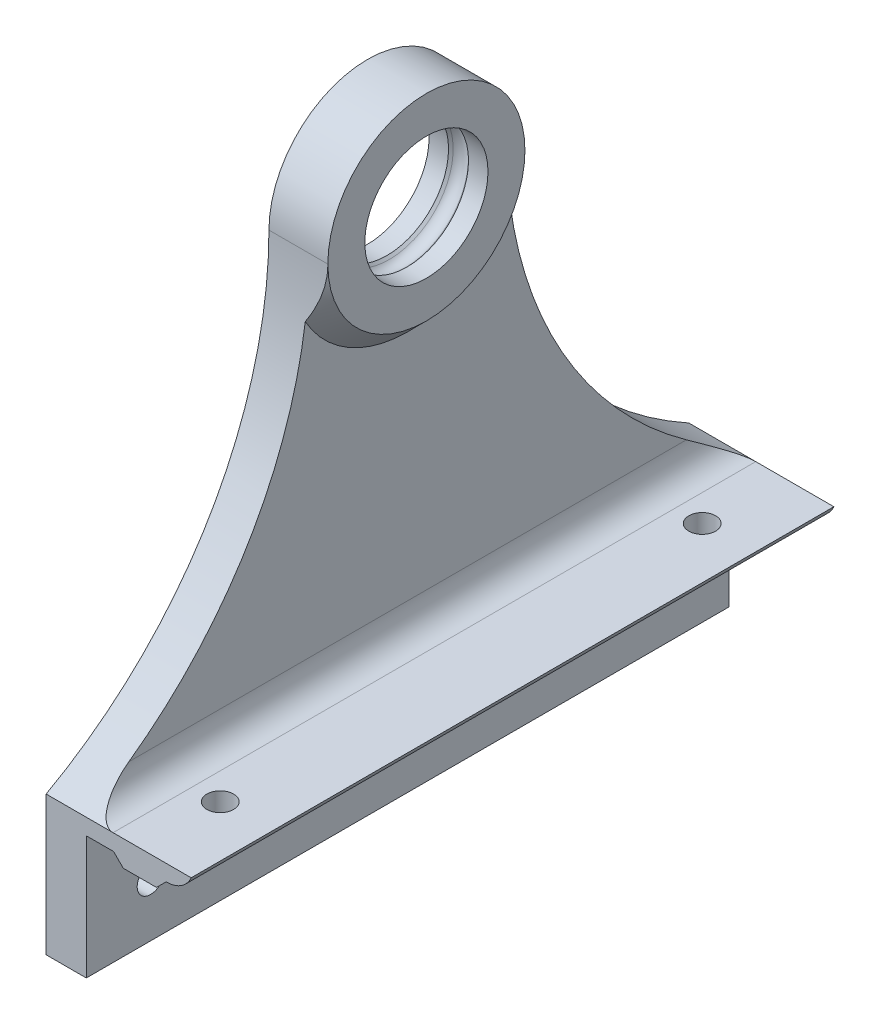
SolidWorks part; units mm, degrees
ref_plane "Front Plane" through (0, 0, 0) normal (0, 0, 1) x (1, 0, 0)
ref_plane "Top Plane" through (0, 0, 0) normal (0, 1, 0) x (1, 0, 0)
ref_plane "Right Plane" through (0, 0, 0) normal (1, 0, 0) x (0, 0, -1)
sketch "Sketch1" plane through (0, 0, 0) normal (0, 0, 1) x (1, 0, 0)
  line L0 (10, 26) -> (10, 20) construction
  line L5 (0, 0) -> (20, 0) construction
  line L6 (0, 0) -> (0, 20) construction
  line L7 (0, 20) -> (20, 20) construction
  line L8 (20, 0) -> (20, 20) construction
  line L9 (5.1, 122) -> (14.9, 122) construction
  line L10 (5.1, 122) -> (5.1, 26) construction
  line L11 (5.1, 26) -> (14.9, 26) construction
  line L12 (14.9, 122) -> (14.9, 26) construction
  line L13 (5.1, 122) -> (14.9, 26) construction
  line L14 (5.1, 26) -> (14.9, 122) construction
  line L15 (10, 74) -> (50010, 74) construction
  point P4 (10, 74)
  dimension "D1" = 20
  dimension "D2" = 96
  dimension "D3" = 9.8
  dimension "D4" = 6
sketch "Sketch2" plane through (0, 0, 0) normal (1, 0, 0) x (0, 0, -1)
  line L0 (-60, 0) -> (60, 0)
  line L1 (0, 0) -> (-54890.8777, 0) construction
  line L2 (-82.83, 20) -> (54808.0478, 20) construction
  line L3 (0, 122) -> (0, 26) construction
  line L4 (-83.1115, 96.39) -> (49916.8885, 96.39) construction
  line L5 (90.3268, 123.67) -> (50090.3268, 123.67) construction
  line L6 (103.2777, 30) -> (50103.2777, 30) construction
  line L7 (-104.869, 57.28) -> (49895.131, 57.28) construction
  line L8 (-60, 0) -> (-60, 26)
  line L9 (60, 0) -> (60, 26)
  circle A1 centre (0, 96.39) radius 11.5
  circle A2 centre (0, 96.39) radius 18.4 construction
  arc A3 (-18.4, 96.39) -> (18.4, 96.39) centre (0, 96.39) cw
  arc A4 (-18.4, 96.39) -> (-60, 26) centre (-98.7523, 96.39) cw
  arc A5 (18.4, 96.39) -> (60, 26) centre (98.7523, 96.39) ccw
  point P4 (0, 0)
  dimension "D3" = 93.67
  dimension "D4" = 23
  dimension "D5" = 36.8
  dimension "D9" = 26
  dimension "D1" = 20
  dimension "D2" = 120
  dimension "D6" = 27.28
  dimension "D7" = 27.28
  dimension "D8" = 10
  dimension "D10" = 26
extrude "Boss-Extrude1" add sketch "Sketch2" against normal blind 7.5
sketch "Sketch3" plane through (0, 0, 0) normal (1, 0, 0) x (0, 0, -1)
  circle A0 centre (0, 96.39) radius 18.4
  circle A1 centre (0, 96.39) radius 11.5
extrude "Boss-Extrude2" add sketch "Sketch3" along normal blind 3.5
chamfer "Chamfer1" distance 3.5 angle 45 1 edges at (0, 77.99, 0)
ref_axis "Axis1" through (-7.5, 96.39, 0) along (1, 0, 0)
sketch "Sketch5" plane through (0, 0, 0) normal (0, 0, 1) x (1, 0, 0)
  line L0 (-7.5, 106.89) -> (3.5, 106.89) construction
  line L1 (-3.4319, 108.3219) -> (-3.8638, 107.89)
  line L2 (-3.8638, 107.89) -> (-0.1362, 107.89)
  line L5 (-7.5, 114.79) -> (-7.5, 96.39) construction
  line L6 (3.5, 96.39) -> (3.5, 114.79) construction
  line L7 (-7.5, 96.39) -> (3.5, 96.39) construction
  line L10 (-7.5, 107.89) -> (3.5, 107.89) construction
  line L11 (-2, 104.89) -> (-2, 50104.89) construction
  line L12 (-0.5681, 108.3219) -> (-0.1362, 107.89)
  circle A0 centre (-2, 106.89) radius 2 construction
  arc A1 (-3.4319, 108.3219) -> (-0.5681, 108.3219) centre (-2, 106.89) cw
  dimension "D2" = 4
  dimension "D3" = 1
  dimension "D4" = 2.025
  dimension "D5" = 45
  dimension "D1" = 10.5
revolve "Cut-Revolve1" cut sketch "Sketch5" angle 360 about axis through (-7.5, 96.39, 0) along (1, 0, 0)
sketch "Sketch6" plane through (0, 0, 0) normal (1, 0, 0) x (0, 0, -1)
  line L0 (-60, 23) -> (60, 23) construction
  line L1 (-60, 0) -> (60, 0) construction
  line L2 (-60, 0) -> (-60, 20) construction
  line L3 (-60, 20) -> (60, 20) construction
  line L4 (60, 0) -> (60, 20) construction
  line L9 (-60, 26) -> (-60, 0) construction
  line L10 (60, 0) -> (60, 26) construction
  line L12 (-60, 23) -> (60, 23)
  line L13 (-60, 23) -> (-60, 26)
  line L14 (-60, 26) -> (60, 26)
  line L15 (60, 23) -> (60, 26)
  dimension "D1" = 20
  dimension "D2" = 120
  dimension "D3" = 3
extrude "Boss-Extrude3" add sketch "Sketch6" along normal blind 20
fillet "Fillet2" radius 5 1 edges at (0, 26, 0)
sketch "Sketch7" plane through (0, 0, -60) normal (0, 0, -1) x (-1, 0, 0)
  line L0 (-20, 23) -> (0, 23) construction
  line L1 (-20, 23) -> (-20, 26) construction
  line L2 (-20, 28) -> (-20, 23)
  line L3 (-20, 23) -> (-15, 23)
  circle A0 centre (-15, 28) radius 5 construction
  arc A1 (-20, 28) -> (-15, 23) centre (-15, 28) ccw
  dimension "D1" = 10
extrude "Cut-Extrude1" cut sketch "Sketch7" against normal through all
sketch "Sketch8" plane through (0, 0, -60) normal (0, 0, -1) x (-1, 0, 0)
  line L0 (-15.942, 21.2) -> (-11.6184, 21.2) construction
  line L1 (-15, 23) -> (0, 23) construction
  line L2 (-14.9, 23) -> (-5.1, 23)
  line L4 (-13.1, 21.2) -> (-6.9, 21.2)
  line L6 (-14.9, 23) -> (-13.1, 21.2)
  line L7 (-5.1, 23) -> (-6.9, 21.2)
  point P7 (-10, 23)
  point P10 (-10, 21.2)
  dimension "D1" = 1.8
extrude "Boss-Extrude4" add sketch "Sketch8" against normal blind 120
sketch "Sketch9" plane through (0, 26, 0) normal (0, 1, 0) x (1, 0, 0)
  line L0 (-66.3921, 0) -> (49933.6079, 0) construction
  line L1 (-7.5, 60) -> (10, 60) construction
  line L2 (-7.5, 60) -> (-7.5, 45) construction
  line L3 (-7.5, 45) -> (10, 45) construction
  line L4 (10, 60) -> (10, 45) construction
  line L6 (10, -60) -> (10, -45) construction
  line L7 (-7.5, -45) -> (10, -45) construction
  line L8 (-7.5, -60) -> (-7.5, -45) construction
  line L9 (-7.5, -60) -> (10, -60) construction
  circle A1 centre (10, 45) radius 2.5
  circle A2 centre (10, -45) radius 2.5
  dimension "D1" = 17.5
  dimension "D2" = 15
extrude "Cut-Extrude2" cut sketch "Sketch9" against normal through all
sketch "Sketch11" plane through (-7.5, 0, 0) normal (-1, 0, 0) x (0, 0, 1)
  line L0 (0, 51.3995) -> (0, -49948.6005) construction
  line L2 (48, 0) -> (48, 10) construction
  line L3 (-60, 0) -> (-48, 0) construction
  line L4 (-60, 0) -> (-60, 10) construction
  line L5 (-60, 10) -> (-48, 10) construction
  line L6 (-48, 0) -> (-48, 10) construction
  line L7 (60, 10) -> (48, 10) construction
  line L8 (60, 0) -> (60, 10) construction
  line L9 (60, 0) -> (48, 0) construction
  circle A0 centre (-48, 10) radius 2.5
  circle A1 centre (48, 10) radius 2.5
  circle A2 centre (0, 10) radius 2.5
  dimension "D1" = 10
  dimension "D2" = 12
extrude "Cut-Extrude3" cut sketch "Sketch11" against normal through all
